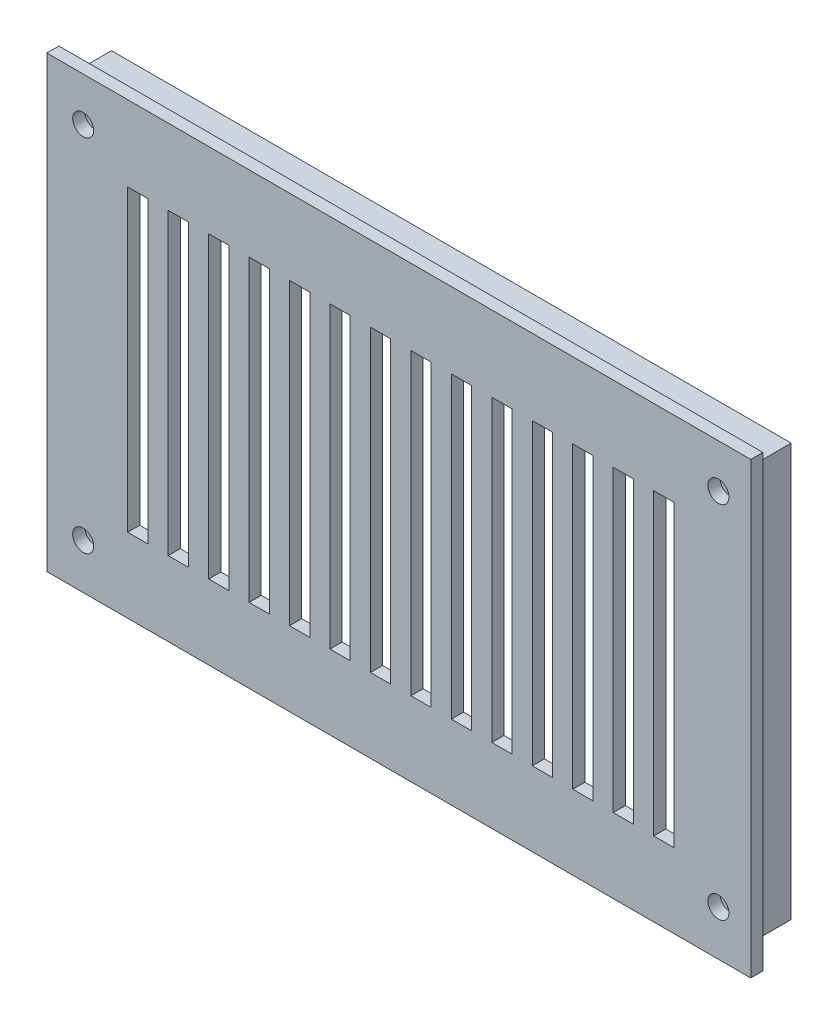
SolidWorks part; units mm, degrees
ref_plane "Front Plane" through (0, 0, 0) normal (0, 0, 1) x (1, 0, 0)
ref_plane "Top Plane" through (0, 0, 0) normal (0, 1, 0) x (1, 0, 0)
ref_plane "Right Plane" through (0, 0, 0) normal (1, 0, 0) x (0, 0, -1)
sketch "Sketch1" plane through (0, 0, 0) normal (0, 0, 1) x (1, 0, 0)
  line L0 (-57, -37.0886) -> (-57, 36.822)
  line L1 (87, 55.5) -> (-87, 55.5)
  line L2 (87, 55.5) -> (87, -55.5)
  line L3 (87, -55.5) -> (-87, -55.5)
  line L4 (-87, 55.5) -> (-87, -55.5)
  line L5 (87, 55.5) -> (-87, -55.5) construction
  line L6 (87, -55.5) -> (-87, 55.5) construction
  line L7 (82, 48.7) -> (-82, 48.7)
  line L8 (82, 48.7) -> (82, -48.7)
  line L9 (82, -48.7) -> (-82, -48.7)
  line L10 (-82, 48.7) -> (-82, -48.7)
  line L11 (82, 48.7) -> (-82, -48.7) construction
  line L12 (82, -48.7) -> (-82, 48.7) construction
  line L13 (-67, -37.0886) -> (-62, -37.0886)
  line L14 (-67, -37.0886) -> (-67, 36.822)
  line L15 (-67, 36.822) -> (-62, 36.822)
  line L16 (-62, -37.0886) -> (-62, 36.822)
  line L17 (-67, -37.0886) -> (-62, 36.822) construction
  line L18 (-67, 36.822) -> (-62, -37.0886) construction
  line L19 (-57, -37.0886) -> (-52, -37.0886)
  line L20 (-52, -37.0886) -> (-52, 36.822)
  line L21 (-57, 36.822) -> (-52, 36.822)
  line L22 (-47, -37.0886) -> (-47, 36.822)
  line L23 (-47, -37.0886) -> (-42, -37.0886)
  line L24 (-42, -37.0886) -> (-42, 36.822)
  line L25 (-47, 36.822) -> (-42, 36.822)
  line L26 (-37, -37.0886) -> (-37, 36.822)
  line L27 (-37, -37.0886) -> (-32, -37.0886)
  line L28 (-32, -37.0886) -> (-32, 36.822)
  line L29 (-37, 36.822) -> (-32, 36.822)
  line L30 (-27, -37.0886) -> (-27, 36.822)
  line L31 (-27, -37.0886) -> (-22, -37.0886)
  line L32 (-22, -37.0886) -> (-22, 36.822)
  line L33 (-27, 36.822) -> (-22, 36.822)
  line L34 (-17, -37.0886) -> (-17, 36.822)
  line L35 (-17, -37.0886) -> (-12, -37.0886)
  line L36 (-12, -37.0886) -> (-12, 36.822)
  line L37 (-17, 36.822) -> (-12, 36.822)
  line L38 (-7, -37.0886) -> (-7, 36.822)
  line L39 (-7, -37.0886) -> (-2, -37.0886)
  line L40 (-2, -37.0886) -> (-2, 36.822)
  line L41 (-7, 36.822) -> (-2, 36.822)
  line L42 (3, -37.0886) -> (3, 36.822)
  line L43 (3, -37.0886) -> (8, -37.0886)
  line L44 (8, -37.0886) -> (8, 36.822)
  line L45 (3, 36.822) -> (8, 36.822)
  line L46 (13, -37.0886) -> (13, 36.822)
  line L47 (13, -37.0886) -> (18, -37.0886)
  line L48 (18, -37.0886) -> (18, 36.822)
  line L49 (13, 36.822) -> (18, 36.822)
  line L50 (23, -37.0886) -> (23, 36.822)
  line L51 (23, -37.0886) -> (28, -37.0886)
  line L52 (28, -37.0886) -> (28, 36.822)
  line L53 (23, 36.822) -> (28, 36.822)
  line L54 (33, -37.0886) -> (33, 36.822)
  line L55 (33, -37.0886) -> (38, -37.0886)
  line L56 (38, -37.0886) -> (38, 36.822)
  line L57 (33, 36.822) -> (38, 36.822)
  line L58 (43, -37.0886) -> (43, 36.822)
  line L59 (43, -37.0886) -> (48, -37.0886)
  line L60 (48, -37.0886) -> (48, 36.822)
  line L61 (43, 36.822) -> (48, 36.822)
  line L62 (53, -37.0886) -> (53, 36.822)
  line L63 (53, -37.0886) -> (58, -37.0886)
  line L64 (58, -37.0886) -> (58, 36.822)
  line L65 (53, 36.822) -> (58, 36.822)
  line L66 (63, -37.0886) -> (63, 36.822)
  line L67 (63, -37.0886) -> (68, -37.0886)
  line L68 (68, -37.0886) -> (68, 36.822)
  line L69 (63, 36.822) -> (68, 36.822)
  circle A0 centre (-78, -44.3) radius 2.6
  circle A1 centre (-78, 44.7) radius 2.6
  circle A2 centre (79, 44.7) radius 2.6
  circle A3 centre (79, -44.3) radius 2.6
  point P0 (0, 0)
  point P14 (-64.5, -0.1333)
  point P18 (0, 0)
  dimension "D9" = 5.2
  dimension "D10" = 5.2
  dimension "D11" = 5.2
  dimension "D12" = 5.2
  dimension "D1" = 89
  dimension "D2" = 157
  dimension "D3" = 174
  dimension "D4" = 111
  dimension "D5" = 97.4
  dimension "D6" = 164
  dimension "D7" = 4
  dimension "D8" = 4
  dimension "D13" = 5
  dimension "D14" = 15
  dimension "D15" = 48.8333
  dimension "D17" = 5
  dimension "D16" = 14
extrude "Boss-Extrude1" add sketch "Sketch1" along normal mid plane 3 contours L7 L10 L9 L8 A3 A2 A1 A0 L16 L13 L14 L15 L0 L21 L20 L19 L22 L25 L24 L23 L26 L29 L28 L27 L30 L33 L32 L31 L34 L37 L36 L35 L38 L41 L40 L39 L42 L45 L44 | L1 L4 L3 L2 L10 L7 L8 L9 region at (84.9361, 0, 0) region at (-0.2454, 0.0628, 0)
sketch "Sketch2" plane through (0, 0, -1.5) normal (0, 0, -1) x (-1, 0, 0)
  circle A0 centre (-79, 44.7) radius 1.25
  circle A1 centre (-79, 44.7) radius 3.25
  circle A4 centre (-79, -44.3) radius 1.25
  circle A5 centre (-79, -44.3) radius 3.25
  circle A6 centre (78, 44.7) radius 1.25
  circle A7 centre (78, 44.7) radius 3.25
  circle A8 centre (78, -44.3) radius 3.25
  circle A9 centre (78, -44.3) radius 1.25
  dimension "D1" = 2.5
  dimension "D2" = 2
  dimension "D3" = 2.5
  dimension "D4" = 2
  dimension "D5" = 2.5
  dimension "D6" = 2.5
  dimension "D7" = 2
  dimension "D8" = 2
extrude "Boss-Extrude2" add sketch "Sketch2" along normal blind 5
sketch "Sketch3" plane through (0, 0, -1.5) normal (0, 0, -1) x (-1, 0, 0)
  line L1 (83, 50) -> (-83, 50)
  line L2 (83, 50) -> (83, -50)
  line L3 (83, -50) -> (-83, -50)
  line L4 (-83, 50) -> (-83, -50)
  line L5 (83, 50) -> (-83, -50) construction
  line L6 (83, -50) -> (-83, 50) construction
  line L7 (84, 51) -> (84, -51)
  line L8 (84, -51) -> (-84, -51)
  line L9 (-84, 51) -> (-84, -51)
  line L10 (84, 51) -> (-84, 51)
  point P0 (0, 0)
  dimension "D1" = 100
  dimension "D2" = 166
  dimension "D3" = 1
extrude "Boss-Extrude3" add sketch "Sketch3" along normal blind 10
fillet "Fillet1" radius 4 4 edges at (-74.75, -44.3, -1.5) (-74.75, 44.7, -1.5) (82.25, 44.7, -1.5) (82.25, -44.3, -1.5)
